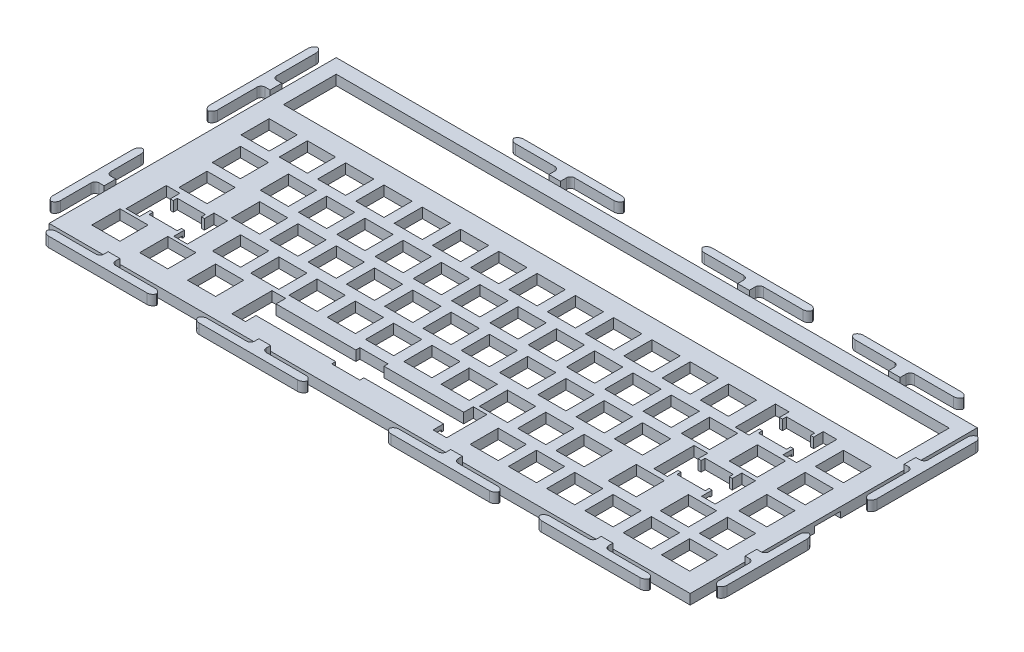
SolidWorks part; units mm, degrees
ref_plane "Front Plane" through (0, 0, 0) normal (0, 0, 1) x (1, 0, 0)
ref_plane "Top Plane" through (0, 0, 0) normal (0, 1, 0) x (1, 0, 0)
ref_plane "Right Plane" through (0, 0, 0) normal (1, 0, 0) x (0, 0, -1)
sketch "Sketch1" plane through (0, 0, 0) normal (0, 1, 0) x (1, 0, 0)
  line L2 (-75.7545, 37.9956) -> (-61.7545, 37.9956)
  line L3 (-94.8265, 37.9956) -> (-80.8265, 37.9956)
  line L4 (-94.8265, 37.9956) -> (-94.8265, 51.9956)
  line L5 (-94.8265, 51.9956) -> (-80.8265, 51.9956)
  line L6 (-80.8265, 37.9956) -> (-80.8265, 51.9956)
  line L7 (-75.7545, 37.9956) -> (-75.7545, 51.9956)
  line L8 (-75.7545, 51.9956) -> (-61.7545, 51.9956)
  line L9 (-61.7545, 37.9956) -> (-61.7545, 51.9956)
  line L10 (133.7495, 37.9956) -> (147.7495, 37.9956)
  line L11 (-37.6545, 37.9956) -> (-23.6545, 37.9956)
  line L12 (-56.7045, 37.9956) -> (-42.7045, 37.9956)
  line L13 (-56.7045, 37.9956) -> (-56.7045, 51.9956)
  line L14 (-56.7045, 51.9956) -> (-42.7045, 51.9956)
  line L15 (-42.7045, 37.9956) -> (-42.7045, 51.9956)
  line L16 (-37.6545, 37.9956) -> (-37.6545, 51.9956)
  line L17 (-37.6545, 51.9956) -> (-23.6545, 51.9956)
  line L18 (-23.6545, 37.9956) -> (-23.6545, 51.9956)
  line L19 (133.7495, 37.9956) -> (133.7495, 51.9956)
  line L20 (133.7495, 51.9956) -> (147.7495, 51.9956)
  line L21 (0.4455, 37.9956) -> (14.4455, 37.9956)
  line L22 (-18.6045, 37.9956) -> (-4.6045, 37.9956)
  line L23 (-18.6045, 37.9956) -> (-18.6045, 51.9956)
  line L24 (-18.6045, 51.9956) -> (-4.6045, 51.9956)
  line L25 (-4.6045, 37.9956) -> (-4.6045, 51.9956)
  line L26 (0.4455, 37.9956) -> (0.4455, 51.9956)
  line L27 (0.4455, 51.9956) -> (14.4455, 51.9956)
  line L28 (14.4455, 37.9956) -> (14.4455, 51.9956)
  line L29 (147.7495, 37.9956) -> (147.7495, 51.9956)
  line L30 (38.5455, 37.9956) -> (52.5455, 37.9956)
  line L31 (19.4955, 37.9956) -> (33.4955, 37.9956)
  line L32 (19.4955, 37.9956) -> (19.4955, 51.9956)
  line L33 (19.4955, 51.9956) -> (33.4955, 51.9956)
  line L34 (33.4955, 37.9956) -> (33.4955, 51.9956)
  line L35 (38.5455, 37.9956) -> (38.5455, 51.9956)
  line L36 (38.5455, 51.9956) -> (52.5455, 51.9956)
  line L37 (52.5455, 37.9956) -> (52.5455, 51.9956)
  line L38 (147.7495, 44.9956) -> (154.1495, 44.9956) construction
  line L39 (167.1835, 18.9456) -> (181.1835, 18.9456)
  line L40 (167.1835, 18.9456) -> (167.1835, 32.9456)
  line L41 (76.6455, 37.9956) -> (90.6455, 37.9956)
  line L42 (57.5955, 37.9956) -> (71.5955, 37.9956)
  line L43 (57.5955, 37.9956) -> (57.5955, 51.9956)
  line L44 (57.5955, 51.9956) -> (71.5955, 51.9956)
  line L45 (71.5955, 37.9956) -> (71.5955, 51.9956)
  line L46 (76.6455, 37.9956) -> (76.6455, 51.9956)
  line L47 (76.6455, 51.9956) -> (90.6455, 51.9956)
  line L48 (90.6455, 37.9956) -> (90.6455, 51.9956)
  line L49 (167.1835, 32.9456) -> (181.1835, 32.9456)
  line L50 (114.7225, 37.9956) -> (128.7225, 37.9956)
  line L51 (95.6955, 37.9956) -> (109.6955, 37.9956)
  line L52 (95.6955, 37.9956) -> (95.6955, 51.9956)
  line L53 (95.6955, 51.9956) -> (109.6955, 51.9956)
  line L54 (109.6955, 37.9956) -> (109.6955, 51.9956)
  line L55 (114.7225, 37.9956) -> (114.7225, 51.9956)
  line L56 (114.7225, 51.9956) -> (128.7225, 51.9956)
  line L57 (128.7225, 37.9956) -> (128.7225, 51.9956)
  line L58 (181.1835, 18.9456) -> (181.1835, 32.9456)
  line L59 (157.3735, 25.9456) -> (167.1835, 25.9456) construction
  line L73 (162.3995, 52.2456) -> (176.3995, 52.2456)
  line L75 (176.3995, 38.2456) -> (162.3995, 38.2456)
  line L77 (176.3995, 52.2456) -> (176.3995, 50.2456)
  line L78 (176.3995, 50.2456) -> (177.8995, 50.2456)
  line L79 (177.8995, 50.2456) -> (177.8995, 54.9956)
  line L80 (177.8995, 54.9956) -> (184.6495, 54.9956)
  line L81 (184.6495, 54.9956) -> (184.6495, 34.9956)
  line L82 (184.6495, 34.9956) -> (177.8995, 34.9956)
  line L83 (177.8995, 34.9956) -> (177.8995, 40.2456)
  line L84 (177.8995, 40.2456) -> (176.3995, 40.2456)
  line L85 (176.3995, 40.2456) -> (176.3995, 38.2456)
  line L86 (162.3995, 52.2456) -> (162.3995, 50.2456)
  line L87 (160.8995, 54.9956) -> (160.8995, 50.2456)
  line L88 (160.8995, 50.2456) -> (162.3995, 50.2456)
  line L89 (160.8995, 54.9956) -> (154.1495, 54.9956)
  line L90 (154.1495, 54.9956) -> (154.1495, 34.9956)
  line L91 (154.1495, 34.9956) -> (160.8995, 34.9956)
  line L92 (160.8995, 34.9956) -> (160.8995, 40.2456)
  line L93 (160.8995, 40.2456) -> (162.3995, 40.2456)
  line L94 (162.3995, 40.2456) -> (162.3995, 38.2456)
  line L116 (-47.1265, 18.9456) -> (-33.1265, 18.9456)
  line L117 (-66.1765, 18.9456) -> (-52.1765, 18.9456)
  line L118 (-66.1765, 18.9456) -> (-66.1765, 32.9456)
  line L119 (-66.1765, 32.9456) -> (-52.1765, 32.9456)
  line L120 (-52.1765, 18.9456) -> (-52.1765, 32.9456)
  line L121 (-47.1265, 18.9456) -> (-47.1265, 32.9456)
  line L122 (-47.1265, 32.9456) -> (-33.1265, 32.9456)
  line L123 (-33.1265, 18.9456) -> (-33.1265, 32.9456)
  line L125 (-9.0515, 18.9456) -> (4.9485, 18.9456)
  line L126 (-28.0765, 18.9456) -> (-14.0765, 18.9456)
  line L127 (-28.0765, 18.9456) -> (-28.0765, 32.9456)
  line L128 (-28.0765, 32.9456) -> (-14.0765, 32.9456)
  line L129 (-14.0765, 18.9456) -> (-14.0765, 32.9456)
  line L130 (-9.0515, 18.9456) -> (-9.0515, 32.9456)
  line L131 (-9.0515, 32.9456) -> (4.9485, 32.9456)
  line L132 (4.9485, 18.9456) -> (4.9485, 32.9456)
  line L135 (29.0735, 18.9456) -> (43.0735, 18.9456)
  line L136 (9.9485, 18.9456) -> (23.9485, 18.9456)
  line L137 (9.9485, 18.9456) -> (9.9485, 32.9456)
  line L138 (9.9485, 32.9456) -> (23.9485, 32.9456)
  line L139 (23.9485, 18.9456) -> (23.9485, 32.9456)
  line L140 (29.0735, 18.9456) -> (29.0735, 32.9456)
  line L141 (29.0735, 32.9456) -> (43.0735, 32.9456)
  line L142 (43.0735, 18.9456) -> (43.0735, 32.9456)
  line L144 (67.1485, 18.9456) -> (81.1485, 18.9456)
  line L145 (48.1235, 18.9456) -> (62.1235, 18.9456)
  line L146 (48.1235, 18.9456) -> (48.1235, 32.9456)
  line L147 (48.1235, 32.9456) -> (62.1235, 32.9456)
  line L148 (62.1235, 18.9456) -> (62.1235, 32.9456)
  line L149 (67.1485, 18.9456) -> (67.1485, 32.9456)
  line L150 (67.1485, 32.9456) -> (81.1485, 32.9456)
  line L151 (81.1485, 18.9456) -> (81.1485, 32.9456)
  line L152 (159.9865, 14.1456) -> (173.9865, 14.1456)
  line L153 (-42.3635, -0.1044) -> (-28.3635, -0.1044)
  line L154 (-61.4135, -0.1044) -> (-47.4135, -0.1044)
  line L155 (105.2735, 18.9456) -> (119.2735, 18.9456)
  line L156 (86.2235, 18.9456) -> (100.2235, 18.9456)
  line L157 (86.2235, 18.9456) -> (86.2235, 32.9456)
  line L158 (86.2235, 32.9456) -> (100.2235, 32.9456)
  line L159 (100.2235, 18.9456) -> (100.2235, 32.9456)
  line L160 (105.2735, 18.9456) -> (105.2735, 32.9456)
  line L161 (105.2735, 32.9456) -> (119.2735, 32.9456)
  line L162 (119.2735, 18.9456) -> (119.2735, 32.9456)
  line L163 (-61.4135, -0.1044) -> (-61.4135, 13.8956)
  line L172 (-94.8265, 37.9956) -> (-94.8265, 32.9456) construction
  line L173 (-61.4135, 13.8956) -> (-47.4135, 13.8956)
  line L174 (-47.4135, -0.1044) -> (-47.4135, 13.8956)
  line L175 (-90.0635, 18.9456) -> (-76.0635, 18.9456)
  line L176 (-90.0635, 18.9456) -> (-90.0635, 32.9456)
  line L177 (-90.0635, 32.9456) -> (-76.0635, 32.9456)
  line L178 (-76.0635, 18.9456) -> (-76.0635, 32.9456)
  line L179 (-94.8265, 32.9456) -> (-90.0635, 32.9456) construction
  line L180 (124.3235, 18.9456) -> (138.3235, 18.9456)
  line L185 (124.3235, 18.9456) -> (124.3235, 32.9456)
  line L186 (124.3235, 32.9456) -> (138.3235, 32.9456)
  line L187 (138.3235, 18.9456) -> (138.3235, 32.9456)
  line L188 (-42.3635, -0.1044) -> (-42.3635, 13.8956)
  line L189 (143.3735, 18.9456) -> (157.3735, 18.9456)
  line L190 (143.3735, 18.9456) -> (143.3735, 32.9456)
  line L191 (143.3735, 32.9456) -> (157.3735, 32.9456)
  line L192 (157.3735, 18.9456) -> (157.3735, 32.9456)
  line L193 (-42.3635, 13.8956) -> (-28.3635, 13.8956)
  line L194 (-28.3635, -0.1044) -> (-28.3635, 13.8956)
  line L195 (-4.2635, -0.1044) -> (9.7365, -0.1044)
  line L196 (-23.3135, -0.1044) -> (-9.3135, -0.1044)
  line L197 (-23.3135, -0.1044) -> (-23.3135, 13.8956)
  line L198 (-23.3135, 13.8956) -> (-9.3135, 13.8956)
  line L199 (-9.3135, -0.1044) -> (-9.3135, 13.8956)
  line L200 (-4.2635, -0.1044) -> (-4.2635, 13.8956)
  line L201 (-4.2635, 13.8956) -> (9.7365, 13.8956)
  line L202 (9.7365, -0.1044) -> (9.7365, 13.8956)
  line L203 (33.8365, -0.1044) -> (47.8365, -0.1044)
  line L204 (14.7865, -0.1044) -> (28.7865, -0.1044)
  line L205 (14.7865, -0.1044) -> (14.7865, 13.8956)
  line L206 (14.7865, 13.8956) -> (28.7865, 13.8956)
  line L207 (28.7865, -0.1044) -> (28.7865, 13.8956)
  line L208 (33.8365, -0.1044) -> (33.8365, 13.8956)
  line L209 (33.8365, 13.8956) -> (47.8365, 13.8956)
  line L210 (47.8365, -0.1044) -> (47.8365, 13.8956)
  line L211 (71.9365, -0.1044) -> (85.9365, -0.1044)
  line L212 (52.8865, -0.1044) -> (66.8865, -0.1044)
  line L213 (52.8865, -0.1044) -> (52.8865, 13.8956)
  line L214 (52.8865, 13.8956) -> (66.8865, 13.8956)
  line L215 (66.8865, -0.1044) -> (66.8865, 13.8956)
  line L216 (71.9365, -0.1044) -> (71.9365, 13.8956)
  line L217 (71.9365, 13.8956) -> (85.9365, 13.8956)
  line L218 (85.9365, -0.1044) -> (85.9365, 13.8956)
  line L219 (110.0365, -0.1044) -> (124.0365, -0.1044)
  line L220 (90.9865, -0.1044) -> (104.9865, -0.1044)
  line L221 (90.9865, -0.1044) -> (90.9865, 13.8956)
  line L222 (90.9865, 13.8956) -> (104.9865, 13.8956)
  line L223 (104.9865, -0.1044) -> (104.9865, 13.8956)
  line L224 (110.0365, -0.1044) -> (110.0365, 13.8956)
  line L225 (110.0365, 13.8956) -> (124.0365, 13.8956)
  line L226 (124.0365, -0.1044) -> (124.0365, 13.8956)
  line L227 (-87.6075, -0.1044) -> (-73.6075, -0.1044)
  line L228 (-87.6075, -0.1044) -> (-87.6075, 13.8956)
  line L229 (-87.6075, 13.8956) -> (-73.6075, 13.8956)
  line L230 (-73.6075, -0.1044) -> (-73.6075, 13.8956)
  line L231 (-90.0635, 18.9456) -> (-90.0635, 13.8956) construction
  line L232 (129.0865, -0.1044) -> (143.0865, -0.1044)
  line L233 (129.0865, -0.1044) -> (129.0865, 13.8956)
  line L234 (129.0865, 13.8956) -> (143.0865, 13.8956)
  line L235 (143.0865, -0.1044) -> (143.0865, 13.8956)
  line L240 (-90.0635, 13.8956) -> (-87.6075, 13.8956) construction
  line L241 (173.9865, 0.1456) -> (159.9865, 0.1456)
  line L242 (173.9865, 14.1456) -> (173.9865, 12.1456)
  line L243 (173.9865, 12.1456) -> (175.4865, 12.1456)
  line L244 (175.4865, 12.1456) -> (175.4865, 16.8956)
  line L245 (175.4865, 16.8956) -> (182.2365, 16.8956)
  line L246 (182.2365, 16.8956) -> (182.2365, -3.1044)
  line L247 (182.2365, -3.1044) -> (175.4865, -3.1044)
  line L248 (175.4865, -3.1044) -> (175.4865, 2.1456)
  line L249 (175.4865, 2.1456) -> (173.9865, 2.1456)
  line L250 (173.9865, 2.1456) -> (173.9865, 0.1456)
  line L251 (159.9865, 14.1456) -> (159.9865, 12.1456)
  line L252 (158.4865, 16.8956) -> (158.4865, 12.1456)
  line L253 (158.4865, 12.1456) -> (159.9865, 12.1456)
  line L254 (158.4865, 16.8956) -> (151.7365, 16.8956)
  line L255 (151.7365, 16.8956) -> (151.7365, -3.1044)
  line L256 (151.7365, -3.1044) -> (158.4865, -3.1044)
  line L257 (158.4865, -3.1044) -> (158.4865, 2.1456)
  line L258 (158.4865, 2.1456) -> (159.9865, 2.1456)
  line L259 (159.9865, 2.1456) -> (159.9865, 0.1456)
  line L260 (143.0865, 12.1456) -> (151.7365, 12.1456) construction
  line L262 (-32.8385, -19.1544) -> (-18.8385, -19.1544)
  line L263 (-51.8885, -19.1544) -> (-37.8885, -19.1544)
  line L264 (-51.8885, -19.1544) -> (-51.8885, -5.1544)
  line L265 (-51.8885, -5.1544) -> (-37.8885, -5.1544)
  line L266 (-37.8885, -19.1544) -> (-37.8885, -5.1544)
  line L267 (-32.8385, -19.1544) -> (-32.8385, -5.1544)
  line L268 (-32.8385, -5.1544) -> (-18.8385, -5.1544)
  line L269 (-18.8385, -19.1544) -> (-18.8385, -5.1544)
  line L270 (5.2615, -19.1544) -> (19.2615, -19.1544)
  line L271 (-13.7885, -19.1544) -> (0.2115, -19.1544)
  line L272 (-13.7885, -19.1544) -> (-13.7885, -5.1544)
  line L273 (-13.7885, -5.1544) -> (0.2115, -5.1544)
  line L274 (0.2115, -19.1544) -> (0.2115, -5.1544)
  line L275 (5.2615, -19.1544) -> (5.2615, -5.1544)
  line L276 (5.2615, -5.1544) -> (19.2615, -5.1544)
  line L277 (19.2615, -19.1544) -> (19.2615, -5.1544)
  line L278 (43.3615, -19.1544) -> (57.3615, -19.1544)
  line L279 (24.3115, -19.1544) -> (38.3115, -19.1544)
  line L280 (24.3115, -19.1544) -> (24.3115, -5.1544)
  line L281 (24.3115, -5.1544) -> (38.3115, -5.1544)
  line L282 (38.3115, -19.1544) -> (38.3115, -5.1544)
  line L283 (43.3615, -19.1544) -> (43.3615, -5.1544)
  line L284 (43.3615, -5.1544) -> (57.3615, -5.1544)
  line L285 (57.3615, -19.1544) -> (57.3615, -5.1544)
  line L286 (81.4615, -19.6544) -> (95.4615, -19.6544)
  line L287 (62.4115, -19.6544) -> (76.4115, -19.6544)
  line L288 (62.4115, -19.6544) -> (62.4115, -5.6544)
  line L289 (62.4115, -5.6544) -> (76.4115, -5.6544)
  line L290 (76.4115, -19.6544) -> (76.4115, -5.6544)
  line L291 (81.4615, -19.6544) -> (81.4615, -5.6544)
  line L292 (81.4615, -5.6544) -> (95.4615, -5.6544)
  line L293 (95.4615, -19.6544) -> (95.4615, -5.6544)
  line L294 (119.5615, -19.6544) -> (133.5615, -19.6544)
  line L295 (100.5115, -19.6544) -> (114.5115, -19.6544)
  line L296 (100.5115, -19.6544) -> (100.5115, -5.6544)
  line L297 (100.5115, -5.6544) -> (114.5115, -5.6544)
  line L298 (114.5115, -19.6544) -> (114.5115, -5.6544)
  line L299 (119.5615, -19.6544) -> (119.5615, -5.6544)
  line L300 (119.5615, -5.6544) -> (133.5615, -5.6544)
  line L301 (133.5615, -19.6544) -> (133.5615, -5.6544)
  line L306 (-83.3445, -5.1544) -> (-69.3445, -5.1544)
  line L307 (145.5235, -19.6544) -> (159.5235, -19.6544)
  line L308 (145.5235, -19.6544) -> (145.5235, -5.6544)
  line L309 (145.5235, -5.6544) -> (159.5235, -5.6544)
  line L310 (159.5235, -19.6544) -> (159.5235, -5.6544)
  line L311 (-69.3445, -19.1544) -> (-83.3445, -19.1544)
  line L331 (171.4855, -19.6544) -> (185.4855, -19.6544)
  line L332 (171.4855, -19.6544) -> (171.4855, -5.6544)
  line L333 (171.4855, -5.6544) -> (185.4855, -5.6544)
  line L334 (185.4855, -19.6544) -> (185.4855, -5.6544)
  line L335 (159.5235, -12.6544) -> (171.4855, -12.6544) construction
  line L336 (-61.4135, -0.1044) -> (-61.4135, -5.1544) construction
  line L337 (-61.4135, -5.1544) -> (-51.8885, -5.1544) construction
  line L338 (-104.4215, 94.9896) -> (-117.5239, 94.9896) construction
  line L339 (-97.2765, 61.6456) -> (207.7235, 61.6456)
  line L340 (190.9955, 18.9456) -> (204.9955, 18.9456)
  line L341 (190.9955, 18.9456) -> (190.9955, 32.9456)
  line L342 (190.9955, 32.9456) -> (204.9955, 32.9456)
  line L343 (204.9955, 18.9456) -> (204.9955, 32.9456)
  line L344 (181.1835, 25.9456) -> (190.9955, 25.9456) construction
  line L345 (190.9745, 37.9956) -> (204.9745, 37.9956)
  line L346 (190.9745, 37.9956) -> (190.9745, 51.9956)
  line L347 (190.9745, 51.9956) -> (204.9745, 51.9956)
  line L348 (204.9745, 37.9956) -> (204.9745, 51.9956)
  line L349 (184.6495, 44.9956) -> (190.9745, 44.9956) construction
  line L350 (190.9425, -0.1044) -> (204.9425, -0.1044)
  line L351 (190.9425, -0.1044) -> (190.9425, 13.8956)
  line L352 (190.9425, 13.8956) -> (204.9425, 13.8956)
  line L353 (204.9425, -0.1044) -> (204.9425, 13.8956)
  line L354 (182.2365, 6.8956) -> (190.9425, 6.8956) construction
  line L355 (190.9855, -19.6544) -> (204.9855, -19.6544)
  line L356 (190.9855, -19.6544) -> (190.9855, -5.6544)
  line L357 (190.9855, -5.6544) -> (204.9855, -5.6544)
  line L358 (204.9855, -19.6544) -> (204.9855, -5.6544)
  line L359 (185.4855, -12.6544) -> (190.9855, -12.6544) construction
  line L360 (-69.3445, -5.1544) -> (-69.3445, -7.1544)
  line L361 (-69.3445, -7.1544) -> (-67.8445, -7.1544)
  line L362 (-67.8445, -7.1544) -> (-67.8445, -2.4044)
  line L363 (-67.8445, -2.4044) -> (-61.0945, -2.4044)
  line L364 (-61.0945, -2.4044) -> (-61.0945, -22.4044)
  line L365 (-61.0945, -22.4044) -> (-67.8445, -22.4044)
  line L366 (-67.8445, -22.4044) -> (-67.8445, -17.1544)
  line L367 (-67.8445, -17.1544) -> (-69.3445, -17.1544)
  line L368 (-69.3445, -17.1544) -> (-69.3445, -19.1544)
  line L369 (-83.3445, -5.1544) -> (-83.3445, -7.1544)
  line L370 (-84.8445, -2.4044) -> (-84.8445, -7.1544)
  line L371 (-84.8445, -7.1544) -> (-83.3445, -7.1544)
  line L372 (-84.8445, -2.4044) -> (-91.5945, -2.4044)
  line L373 (-91.5945, -2.4044) -> (-91.5945, -22.4044)
  line L374 (-91.5945, -22.4044) -> (-84.8445, -22.4044)
  line L375 (-84.8445, -22.4044) -> (-84.8445, -17.1544)
  line L376 (-84.8445, -17.1544) -> (-83.3445, -17.1544)
  line L377 (-83.3445, -17.1544) -> (-83.3445, -19.1544)
  line L378 (-93.0945, -37.9544) -> (-79.0945, -37.9544)
  line L379 (-93.0945, -37.9544) -> (-93.0945, -23.9544)
  line L380 (-93.0945, -23.9544) -> (-79.0945, -23.9544)
  line L381 (-79.0945, -37.9544) -> (-79.0945, -23.9544)
  line L382 (-69.2945, -37.9544) -> (-55.2945, -37.9544)
  line L383 (-69.2945, -37.9544) -> (-69.2945, -23.9544)
  line L384 (-69.2945, -23.9544) -> (-55.2945, -23.9544)
  line L385 (-55.2945, -37.9544) -> (-55.2945, -23.9544)
  line L390 (-45.4945, -37.9544) -> (-31.4945, -37.9544)
  line L391 (-45.4945, -37.9544) -> (-45.4945, -23.9544)
  line L392 (-45.4945, -23.9544) -> (-31.4945, -23.9544)
  line L393 (-31.4945, -37.9544) -> (-31.4945, -23.9544)
  line L394 (-55.2945, -23.9544) -> (-45.4945, -23.9544) construction
  line L395 (26.4395, -24.1144) -> (40.4395, -24.1144)
  line L396 (40.4395, -38.1144) -> (26.4395, -38.1144)
  line L397 (40.4395, -24.1144) -> (40.4395, -26.1144)
  line L398 (40.4395, -26.1144) -> (80.1235, -26.1144)
  line L399 (80.1235, -26.1144) -> (80.1235, -21.3644)
  line L400 (80.1235, -21.3644) -> (86.8735, -21.3644)
  line L401 (86.8735, -21.3644) -> (86.8735, -41.3644)
  line L402 (86.8735, -41.3644) -> (80.1235, -41.3644)
  line L403 (80.1235, -41.3644) -> (80.1235, -36.1144)
  line L404 (80.1235, -36.1144) -> (40.4395, -36.1144)
  line L405 (40.4395, -36.1144) -> (40.4395, -38.1144)
  line L406 (26.4395, -24.1144) -> (26.4395, -26.1144)
  line L407 (-13.2445, -21.3644) -> (-13.2445, -26.1144)
  line L408 (-13.2445, -26.1144) -> (26.4395, -26.1144)
  line L409 (-13.2445, -21.3644) -> (-19.9945, -21.3644)
  line L410 (-19.9945, -21.3644) -> (-19.9945, -41.3644)
  line L411 (-19.9945, -41.3644) -> (-13.2445, -41.3644)
  line L412 (-13.2445, -41.3644) -> (-13.2445, -36.1144)
  line L413 (-13.2445, -36.1144) -> (26.4395, -36.1144)
  line L414 (26.4395, -36.1144) -> (26.4395, -38.1144)
  line L415 (95.5435, -38.3644) -> (109.5435, -38.3644)
  line L416 (95.5435, -38.3644) -> (95.5435, -24.3644)
  line L417 (95.5435, -24.3644) -> (109.5435, -24.3644)
  line L418 (109.5435, -38.3644) -> (109.5435, -24.3644)
  line L419 (86.8735, -31.3644) -> (95.5435, -31.3644) construction
  line L420 (114.5935, -38.3644) -> (128.5935, -38.3644)
  line L421 (114.5935, -38.3644) -> (114.5935, -24.3644)
  line L422 (114.5935, -24.3644) -> (128.5935, -24.3644)
  line L423 (128.5935, -38.3644) -> (128.5935, -24.3644)
  line L424 (114.5935, -31.3644) -> (109.5435, -31.3644) construction
  line L425 (133.6435, -38.3644) -> (147.6435, -38.3644)
  line L426 (133.6435, -38.3644) -> (133.6435, -24.3644)
  line L427 (133.6435, -24.3644) -> (147.6435, -24.3644)
  line L428 (147.6435, -38.3644) -> (147.6435, -24.3644)
  line L429 (152.6935, -38.3644) -> (166.6935, -38.3644)
  line L430 (152.6935, -38.3644) -> (152.6935, -24.3644)
  line L431 (152.6935, -24.3644) -> (166.6935, -24.3644)
  line L432 (166.6935, -38.3644) -> (166.6935, -24.3644)
  line L433 (171.7435, -38.3644) -> (185.7435, -38.3644)
  line L434 (171.7435, -38.3644) -> (171.7435, -24.3644)
  line L435 (171.7435, -24.3644) -> (185.7435, -24.3644)
  line L436 (185.7435, -38.3644) -> (185.7435, -24.3644)
  line L437 (190.7935, -38.3644) -> (204.7935, -38.3644)
  line L438 (190.7935, -38.3644) -> (190.7935, -24.3644)
  line L439 (190.7935, -24.3644) -> (204.7935, -24.3644)
  line L440 (204.7935, -38.3644) -> (204.7935, -24.3644)
  line L441 (-97.2765, 61.6456) -> (-97.2765, 87.8456)
  line L442 (-97.2765, 87.8456) -> (207.7235, 87.8456)
  line L443 (207.7235, 61.6456) -> (207.7235, 87.8456)
  line L444 (-104.4215, 94.9896) -> (214.5785, 94.9896)
  line L445 (-104.4215, 94.9896) -> (-104.4215, -47.8854)
  line L446 (-104.4215, -47.8854) -> (214.5785, -47.8854)
  line L447 (214.5785, 94.9896) -> (214.5785, -47.8854)
  line L448 (-117.5239, 94.9896) -> (-117.5239, 25.8096) construction
  line L449 (-104.4215, -47.8854) -> (-117.5239, -47.8854) construction
  line L450 (-117.5239, -47.8854) -> (-117.5239, 14.6046) construction
  line L451 (-150.5498, 25.8096) -> (-98.6233, 25.8096) construction
  line L452 (-150.5498, 14.6046) -> (-97.2765, 14.6046) construction
  line L453 (-104.4215, 94.9896) -> (-104.4215, 60.3996) construction
  point P115 (128.7225, 44.9956)
  point P116 (154.1495, 44.9956)
  dimension "D1" = 14
  dimension "D2" = 20
  dimension "D3" = 4.75
  dimension "D4" = 6.75
  dimension "D5" = 1.5
  dimension "D6" = 2
  dimension "D13" = 14
  dimension "D14" = 14
  dimension "D15" = 5.072
  dimension "D16" = 14
  dimension "D17" = 5.05
  dimension "D18" = 5.05
  dimension "D19" = 14
  dimension "D20" = 4.763
  dimension "D21" = 5.05
  dimension "D22" = 9.887
  dimension "D23" = 26.2
  dimension "D24" = 14
  dimension "D25" = 14
  dimension "D26" = 5.05
  dimension "D27" = 5.05
  dimension "D28" = 5.05
  dimension "D29" = 5.05
  dimension "D30" = 5.05
  dimension "D31" = 5.05
  dimension "D32" = 5.05
  dimension "D33" = 5.05
  dimension "D34" = 5.05
  dimension "D35" = 5.027
  dimension "D36" = 5.05
  dimension "D37" = 5.05
  dimension "D38" = 5.025
  dimension "D39" = 5
  dimension "D40" = 5.125
  dimension "D41" = 5.05
  dimension "D42" = 5.025
  dimension "D43" = 5.075
  dimension "D44" = 5.05
  dimension "D45" = 5.05
  dimension "D46" = 5.027
  dimension "D47" = 14.65
  dimension "D48" = 14
  dimension "D49" = 9.81
  dimension "D50" = 12.194
  dimension "D51" = 5.05
  dimension "D52" = 5.05
  dimension "D53" = 5.05
  dimension "D54" = 5.05
  dimension "D55" = 5.05
  dimension "D56" = 5.05
  dimension "D57" = 5.05
  dimension "D58" = 5.05
  dimension "D59" = 5.05
  dimension "D60" = 5.05
  dimension "D61" = 14
  dimension "D62" = 20
  dimension "D63" = 5.05
  dimension "D64" = 2.456
  dimension "D65" = 4.75
  dimension "D66" = 6.75
  dimension "D67" = 1.5
  dimension "D68" = 2
  dimension "D69" = 16.9
  dimension "D70" = 14
  dimension "D71" = 5.05
  dimension "D72" = 5.05
  dimension "D73" = 5.05
  dimension "D74" = 5.05
  dimension "D75" = 5.05
  dimension "D76" = 5.05
  dimension "D77" = 5.05
  dimension "D78" = 5.05
  dimension "D79" = 5.05
  dimension "D80" = 11.962
  dimension "D81" = 20
  dimension "D82" = 14
  dimension "D83" = 11.962
  dimension "D84" = 14
  dimension "D85" = 14
  dimension "D86" = 9.812
  dimension "D87" = 14
  dimension "D88" = 14.575
  dimension "D89" = 4.75
  dimension "D90" = 14
  dimension "D91" = 6.75
  dimension "D92" = 14
  dimension "D93" = 16.956
  dimension "D94" = 14
  dimension "D95" = 5.5
  dimension "D96" = 5.05
  dimension "D97" = 5.05
  dimension "D98" = 9.525
  dimension "D99" = 1.5
  dimension "D100" = 2
  dimension "D101" = 5.05
  dimension "D102" = 9.206
  dimension "D103" = 5.05
  dimension "D104" = 14
  dimension "D105" = 14
  dimension "D106" = 14
  dimension "D107" = 14
  dimension "D108" = 1.5
  dimension "D109" = 9.8
  dimension "D110" = 5.05
  dimension "D111" = 9.8
  dimension "D112" = 5.05
  dimension "D113" = 5.05
  dimension "D114" = 14
  dimension "D115" = 14
  dimension "D116" = 20
  dimension "D117" = 4.75
  dimension "D118" = 6.75
  dimension "D119" = 39.684
  dimension "D120" = 2
  dimension "D121" = 5.05
  dimension "D122" = 11.5
  dimension "D123" = 14
  dimension "D124" = 8.67
  dimension "D125" = 5.25
  dimension "D126" = 14
  dimension "D127" = 5.05
  dimension "D128" = 14
  dimension "D129" = 14
  dimension "D130" = 14
  dimension "D131" = 14
  dimension "D132" = 5.05
  dimension "D133" = 5.05
  dimension "D134" = 5.05
  dimension "D135" = 5.05
  dimension "D136" = 4.8
  dimension "D137" = 5.25
  dimension "D138" = 5.25
  dimension "D139" = 5.25
  dimension "D140" = 305
  dimension "D141" = 9.65
  dimension "D142" = 142.875
  dimension "D143" = 319
  dimension "D144" = 7.144
  dimension "D145" = 7.145
  dimension "D146" = 2.45
  dimension "D147" = 69.18
  dimension "D148" = 62.49
extrude "Boss-Extrude2" add sketch "Sketch1" along normal mid plane 5
sketch "Sketch2" plane through (0, 2.5, 0) normal (0, 1, 0) x (1, 0, 0)
  line L0 (-104.4215, 25.7896) -> (-104.4215, 14.6146) construction
  line L1 (-104.4215, -47.8854) -> (-104.4215, -20.4854) construction
  line L2 (-104.4215, 94.9896) -> (-104.4215, -47.8854) construction
  line L14 (-107.4215, 20.2021) -> (-104.4215, 20.2021) construction
  line L16 (-107.4215, 31.2421) -> (-107.4215, 9.1621) construction
  line L25 (214.5785, 64.3896) -> (214.5785, 58.5896)
  line L26 (55.1185, 125.3194) -> (55.1185, -78.0627) construction
  line L44 (214.5785, 58.5896) -> (218.6785, 58.5896)
  line L45 (218.6785, 58.5896) -> (218.6785, 33.9896)
  line L46 (218.6785, 33.9896) -> (222.6785, 33.9896)
  line L47 (222.6785, 33.9896) -> (222.6785, 88.9896)
  line L48 (55.0785, 94.9896) -> (55.0785, -47.8854) construction
  line L49 (214.5785, 94.9896) -> (-104.4215, 94.9896) construction
  line L50 (-104.4215, -47.8854) -> (214.5785, -47.8854) construction
  line L51 (55.1185, 23.6283) -> (270.1989, 23.6283) construction
  line L52 (55.1185, 23.6283) -> (-168.679, 23.6283) construction
  line L55 (45.7235, 94.9896) -> (56.8285, 94.9896) construction
  line L56 (51.276, 94.9896) -> (51.276, 98.9896) construction
  line L57 (40.236, 98.9896) -> (62.316, 98.9896) construction
  line L74 (222.6785, 88.9896) -> (218.6785, 88.9896)
  line L75 (214.5785, 94.9896) -> (176.1966, 94.9896) construction
  line L124 (55.0785, -47.8854) -> (95.4285, -47.8854) construction
  line L125 (-104.4215, 67.8896) -> (-104.4215, 62.0896)
  line L127 (45.7225, -47.8854) -> (56.8335, -47.8854) construction
  line L128 (51.278, -47.8854) -> (51.278, -52.8854) construction
  line L129 (40.276, -52.8854) -> (62.356, -52.8854) construction
  line L134 (-104.4215, 62.0896) -> (-108.9215, 62.0896)
  line L135 (-108.9215, 62.0896) -> (-108.9215, 37.4896)
  line L136 (-108.9215, 37.4896) -> (-112.9215, 37.4896)
  line L137 (-112.9215, 37.4896) -> (-112.9215, 92.4896)
  line L138 (-112.9215, 92.4896) -> (-108.9215, 92.4896)
  line L139 (-108.9215, 92.4896) -> (-108.9215, 67.8896)
  line L140 (-108.9215, 67.8896) -> (-104.4215, 67.8896)
  line L141 (-104.4215, 94.9896) -> (-104.4215, 67.8896) construction
  line L142 (-104.4215, -14.6854) -> (-104.4215, -20.4854)
  line L143 (-104.4215, -20.4854) -> (-108.9215, -20.4854)
  line L144 (-108.9215, -20.4854) -> (-108.9215, -40.5854)
  line L145 (-108.9215, -40.5854) -> (-112.9215, -40.5854)
  line L146 (-112.9215, -40.5854) -> (-112.9215, 5.4146)
  line L147 (-112.9215, 5.4146) -> (-108.9215, 5.4146)
  line L148 (-108.9215, 5.4146) -> (-108.9215, -14.6854)
  line L149 (-108.9215, -14.6854) -> (-104.4215, -14.6854)
  line L150 (1.3585, 94.9896) -> (7.1585, 94.9896)
  line L151 (7.1585, 94.9896) -> (7.1585, 99.9896)
  line L152 (7.1585, 99.9896) -> (31.7585, 99.9896)
  line L153 (31.7585, 99.9896) -> (31.7585, 103.9896)
  line L154 (31.7585, 103.9896) -> (-23.2415, 103.9896)
  line L155 (-23.2415, 103.9896) -> (-23.2415, 99.9896)
  line L156 (-23.2415, 99.9896) -> (1.3585, 99.9896)
  line L157 (1.3585, 99.9896) -> (1.3585, 94.9896)
  line L158 (55.0785, 94.9896) -> (7.1585, 94.9896) construction
  line L166 (-75.0215, -47.8854) -> (-69.2215, -47.8854)
  line L167 (-69.2215, -47.8854) -> (-69.2215, -51.9854)
  line L168 (-69.2215, -51.9854) -> (-44.6215, -51.9854)
  line L169 (-44.6215, -51.9854) -> (-44.6215, -55.9854)
  line L170 (-44.6215, -55.9854) -> (-99.6215, -55.9854)
  line L171 (-99.6215, -55.9854) -> (-99.6215, -51.9854)
  line L172 (-99.6215, -51.9854) -> (-75.0215, -51.9854)
  line L173 (-75.0215, -51.9854) -> (-75.0215, -47.8854)
  line L174 (-0.0215, -47.8854) -> (5.7785, -47.8854)
  line L175 (5.7785, -47.8854) -> (5.7785, -51.9854)
  line L176 (5.7785, -51.9854) -> (30.3785, -51.9854)
  line L177 (30.3785, -51.9854) -> (30.3785, -55.9854)
  line L178 (30.3785, -55.9854) -> (-24.6215, -55.9854)
  line L179 (-24.6215, -55.9854) -> (-24.6215, -51.9854)
  line L180 (-24.6215, -51.9854) -> (-0.0215, -51.9854)
  line L181 (-0.0215, -51.9854) -> (-0.0215, -47.8854)
  line L182 (-104.4215, -47.8854) -> (-75.0215, -47.8854) construction
  line L183 (95.4285, -47.8854) -> (101.2285, -47.8854)
  line L184 (101.2285, -47.8854) -> (101.2285, -51.9854)
  line L185 (101.2285, -51.9854) -> (125.8285, -51.9854)
  line L186 (125.8285, -51.9854) -> (125.8285, -55.9854)
  line L187 (125.8285, -55.9854) -> (70.8285, -55.9854)
  line L188 (70.8285, -55.9854) -> (70.8285, -51.9854)
  line L189 (70.8285, -51.9854) -> (95.4285, -51.9854)
  line L190 (95.4285, -51.9854) -> (95.4285, -47.8854)
  line L191 (170.3285, -47.8854) -> (176.1285, -47.8854)
  line L192 (176.1285, -47.8854) -> (176.1285, -51.9854)
  line L193 (176.1285, -51.9854) -> (200.7285, -51.9854)
  line L194 (200.7285, -51.9854) -> (200.7285, -55.9854)
  line L195 (200.7285, -55.9854) -> (145.7285, -55.9854)
  line L196 (145.7285, -55.9854) -> (145.7285, -51.9854)
  line L197 (145.7285, -51.9854) -> (170.3285, -51.9854)
  line L198 (170.3285, -51.9854) -> (170.3285, -47.8854)
  line L199 (55.0785, -47.8854) -> (5.7785, -47.8854) construction
  line L200 (95.3145, 94.9896) -> (101.1145, 94.9896)
  line L201 (101.1145, 94.9896) -> (101.1145, 99.9896)
  line L202 (101.1145, 99.9896) -> (125.7145, 99.9896)
  line L203 (125.7145, 99.9896) -> (125.7145, 103.9896)
  line L204 (125.7145, 103.9896) -> (70.7145, 103.9896)
  line L205 (70.7145, 103.9896) -> (70.7145, 99.9896)
  line L206 (70.7145, 99.9896) -> (95.3145, 99.9896)
  line L207 (95.3145, 99.9896) -> (95.3145, 94.9896)
  line L208 (170.3966, 94.9896) -> (176.1966, 94.9896)
  line L209 (176.1966, 94.9896) -> (176.1966, 99.9896)
  line L210 (176.1966, 99.9896) -> (200.7966, 99.9896)
  line L211 (200.7966, 99.9896) -> (200.7966, 103.9896)
  line L212 (200.7966, 103.9896) -> (145.7966, 103.9896)
  line L213 (145.7966, 103.9896) -> (145.7966, 99.9896)
  line L214 (145.7966, 99.9896) -> (170.3966, 99.9896)
  line L215 (170.3966, 99.9896) -> (170.3966, 94.9896)
  line L216 (214.5785, -47.8854) -> (176.1285, -47.8854) construction
  line L217 (218.6785, 88.9896) -> (218.6785, 64.3896)
  line L218 (218.6785, 64.3896) -> (214.5785, 64.3896)
  line L219 (214.5785, -14.7854) -> (214.5785, -20.5854)
  line L220 (214.5785, -20.5854) -> (218.6785, -20.5854)
  line L221 (218.6785, -20.5854) -> (218.6785, -40.6854)
  line L222 (218.6785, -40.6854) -> (222.6785, -40.6854)
  line L223 (222.6785, -40.6854) -> (222.6785, 5.3146)
  line L224 (222.6785, 5.3146) -> (218.6785, 5.3146)
  line L225 (218.6785, 5.3146) -> (218.6785, -14.7854)
  line L226 (218.6785, -14.7854) -> (214.5785, -14.7854)
  line L227 (214.5785, 94.9896) -> (214.5785, 64.3896) construction
  line L228 (214.5785, -47.8854) -> (214.5785, 94.9896) construction
  line L229 (214.5785, -47.8854) -> (214.5785, -20.5854) construction
  point P28 (-104.4215, 20.2021)
  point P84 (51.276, 98.9896)
  dimension "D4" = 5.8
  dimension "D5" = 4.5
  dimension "D6" = 55
  dimension "D7" = 22.08
  dimension "D8" = 4
  dimension "D9" = 5.8
  dimension "D10" = 4.5
  dimension "D11" = 4
  dimension "D12" = 46
  dimension "D13" = 27.1
  dimension "D14" = 5.8
  dimension "D15" = 4.1
  dimension "D16" = 4
  dimension "D17" = 27.4
  dimension "D18" = 47.92
  dimension "D19" = 4
  dimension "D20" = 22.08
  dimension "D21" = 40.196
  dimension "D22" = 55
  dimension "D23" = 5.8
  dimension "D24" = 4
  dimension "D25" = 46
  dimension "D26" = 30.6
  dimension "D27" = 27.3
  dimension "D29" = 4.1
  dimension "D31" = 38.45
  dimension "D32" = 5.8
  dimension "D33" = 5
  dimension "D34" = 22.08
  dimension "D35" = 5.8
  dimension "D36" = 5
  dimension "D37" = 4
  dimension "D38" = 55
  dimension "D39" = 40.35
  dimension "D40" = 5.8
  dimension "D41" = 4
  dimension "D42" = 55
  dimension "D43" = 4
  dimension "D44" = 55
  dimension "D45" = 4.1
  dimension "D46" = 4.1
  dimension "D47" = 29.4
  dimension "D48" = 5.8
  dimension "D49" = 4
  dimension "D50" = 55
  dimension "D51" = 4.1
  dimension "D52" = 5.8
  dimension "D53" = 4
  dimension "D54" = 55
  dimension "D55" = 4.1
  dimension "D56" = 49.3
  dimension "D57" = 5
  dimension "D58" = 55
  dimension "D59" = 5
  dimension "D60" = 55
extrude "Boss-Extrude3" add sketch "Sketch2" along normal mid plane 5
sketch "Sketch3" plane through (0, 2.5, 0) normal (0, 1, 0) x (1, 0, 0)
  line L0 (208.0785, 94.9896) -> (208.0785, 26.9896) construction
  line L1 (214.5785, 94.9896) -> (176.1966, 94.9896) construction
  line L2 (208.0785, 26.9896) -> (208.0785, 13.9896) construction
  line L3 (214.5785, -14.7854) -> (214.5785, 58.5896) construction
  line L4 (208.0785, 26.9896) -> (208.0785, 13.9896)
  line L5 (208.0785, 13.9896) -> (214.5785, 13.9896)
  line L6 (214.5785, 13.9896) -> (214.5785, 26.9896)
  line L7 (214.5785, 26.9896) -> (208.0785, 26.9896)
  line L8 (58.5785, 89.4896) -> (214.5785, 89.4896) construction
  line L9 (214.5785, 64.3896) -> (214.5785, 94.9896) construction
  line L10 (95.3145, 94.9896) -> (7.1585, 94.9896) construction
  line L11 (58.5785, 89.4896) -> (46.5792, 89.4896)
  line L12 (46.5792, 89.4896) -> (46.5792, 94.9896)
  line L13 (46.5792, 94.9896) -> (58.5785, 94.9896)
  line L14 (58.5785, 94.9896) -> (58.5785, 89.4896)
  line L15 (-97.4215, 94.9896) -> (-97.4215, 26.9896) construction
  line L16 (1.3585, 94.9896) -> (-104.4215, 94.9896) construction
  line L17 (-97.4215, 26.9896) -> (-97.4215, 13.9896) construction
  line L18 (-104.4215, 62.0896) -> (-104.4215, -14.6854) construction
  line L19 (-97.4215, 26.9896) -> (-104.4215, 26.9896)
  line L20 (-104.4215, 26.9896) -> (-104.4215, 13.9896)
  line L21 (-104.4215, 13.9896) -> (-97.4215, 13.9896)
  line L22 (-97.4215, 13.9896) -> (-97.4215, 26.9896)
  dimension "D1" = 68
  dimension "D2" = 13
  dimension "D3" = 6.5
  dimension "D4" = 156
  dimension "D5" = 5.5
  dimension "D6" = 180
  dimension "D7" = 7
extrude "Cut-Extrude1" cut sketch "Sketch3" against normal through all
sketch "Sketch4" plane through (175.4865, 0, 0) normal (1, 0, 0) x (0, 0, -1)
  line L12 (2.1456, -2.5) -> (-3.1044, -2.5)
  line L15 (-3.1044, -2.5) -> (-3.1044, 0.5)
  line L16 (-3.1044, 2.5) -> (-3.1044, -2.5) construction
  line L17 (-3.1044, 0.5) -> (1.1456, 0.5)
  line L18 (1.1456, 0.5) -> (1.1456, 0)
  line L19 (1.1456, 0) -> (2.1456, 0)
  line L20 (2.1456, 2.5) -> (2.1456, -2.5) construction
  line L21 (2.1456, 0) -> (2.1456, -2.5)
  dimension "D1" = 3
  dimension "D2" = 4.25
extrude "Cut-Extrude2" cut sketch "Sketch4" against normal blind 18
sketch "Sketch6" plane through (177.8995, 0, 0) normal (1, 0, 0) x (0, 0, -1)
  line L8 (34.9956, -2.5) -> (34.9956, 0.5)
  line L9 (34.9956, 2.5) -> (34.9956, -2.5) construction
  line L11 (34.9956, 0.5) -> (39.2456, 0.5)
  line L12 (39.2456, 0.5) -> (39.2456, -0.5)
  line L13 (39.2456, -0.5) -> (40.2456, -0.5)
  line L14 (40.2456, 2.5) -> (40.2456, -2.5) construction
  line L15 (40.2456, -0.5) -> (40.2456, -2.5)
  line L16 (40.2456, -2.5) -> (34.9956, -2.5)
  dimension "D1" = 4.25
  dimension "D2" = 3
  dimension "D3" = 2
extrude "Cut-Extrude3" cut sketch "Sketch6" against normal blind 18
sketch "Sketch7" plane through (-67.8445, 0, 0) normal (1, 0, 0) x (0, 0, -1)
  line L12 (-22.4044, -2.5) -> (-22.4044, 0.5)
  line L13 (-22.4044, 0.5) -> (-18.1544, 0.5)
  line L14 (-18.1544, 0.5) -> (-18.1544, -0.5)
  line L15 (-18.1544, -0.5) -> (-17.1544, -0.5)
  line L16 (-17.1544, -0.5) -> (-17.1544, -2.5)
  line L17 (-17.1544, -2.5) -> (-22.4044, -2.5)
  dimension "D4" = 4.25
  dimension "D5" = 3
  dimension "D6" = 2
extrude "Cut-Extrude4" cut sketch "Sketch7" against normal blind 18
sketch "Sketch8" plane through (80.1235, 0, 0) normal (1, 0, 0) x (0, 0, -1)
  line L6 (-41.3644, -2.5) -> (-41.3644, 0.5)
  line L7 (-41.3644, 0.5) -> (-37.1144, 0.5)
  line L8 (-37.1144, 0.5) -> (-37.1144, -0.5)
  line L9 (-37.1144, -0.5) -> (-36.1144, -0.5)
  line L10 (-36.1144, -0.5) -> (-36.1144, -2.5)
  line L11 (-36.1144, -2.5) -> (-41.3644, -2.5)
  dimension "D1" = 4.25
  dimension "D2" = 3
  dimension "D3" = 2
extrude "Cut-Extrude5" cut sketch "Sketch8" against normal blind 95
sketch "Sketch9" plane through (175.4865, 0, 0) normal (1, 0, 0) x (0, 0, -1)
fillet "Fillet1" radius 2 22 edges at (-108.9215, 2.5, 20.4854) (-108.9215, 2.5, 14.6854) (-75.0215, 2.5, 51.9854) (-69.2215, 2.5, 51.9854) (5.7785, 2.5, 51.9854) (-0.0215, 2.5, 51.9854) (95.4285, 2.5, 51.9854) (101.2285, 2.5, 51.9854) (176.1285, 2.5, 51.9854) (170.3285, 2.5, 51.9854) (218.6785, 2.5, 14.7854) (218.6785, 2.5, 20.5854) (218.6785, 2.5, -64.3896) (218.6785, 2.5, -58.5896) (176.1966, 2.5, -99.9896) (170.3966, 2.5, -99.9896) (101.1145, 2.5, -99.9896) (95.3145, 2.5, -99.9896) (1.3585, 2.5, -99.9896) (7.1585, 2.5, -99.9896) (-108.9215, 2.5, -67.8896) (-108.9215, 2.5, -62.0896)
fillet "Fillet2" radius 3 44 edges at (-112.9215, 2.5, -92.4896) (-108.9215, 2.5, -92.4896) (-108.9215, 2.5, -37.4896) (-112.9215, 2.5, -37.4896) (-108.9215, 2.5, -5.4146) (-112.9215, 2.5, -5.4146) (-108.9215, 2.5, 40.5854) (-112.9215, 2.5, 40.5854) (-44.6215, 2.5, 55.9854) (-44.6215, 2.5, 51.9854) (-99.6215, 2.5, 55.9854) (-99.6215, 2.5, 51.9854) (-24.6215, 2.5, 55.9854) (-24.6215, 2.5, 51.9854) (30.3785, 2.5, 55.9854) (30.3785, 2.5, 51.9854) (125.8285, 2.5, 55.9854) (125.8285, 2.5, 51.9854) (70.8285, 2.5, 55.9854) (70.8285, 2.5, 51.9854) (145.7285, 2.5, 55.9854) (145.7285, 2.5, 51.9854) (200.7285, 2.5, 55.9854) (200.7285, 2.5, 51.9854) (222.6785, 2.5, -5.3146) (218.6785, 2.5, -5.3146) (218.6785, 2.5, 40.6854) (222.6785, 2.5, 40.6854) (218.6785, 2.5, -33.9896) (222.6785, 2.5, -33.9896) (222.6785, 2.5, -88.9896) (218.6785, 2.5, -88.9896) (200.7966, 2.5, -103.9896) (200.7966, 2.5, -99.9896) (145.7966, 2.5, -99.9896) (145.7966, 2.5, -103.9896) (125.7145, 2.5, -99.9896) (125.7145, 2.5, -103.9896) (70.7145, 2.5, -99.9896) (70.7145, 2.5, -103.9896) (31.7585, 2.5, -99.9896) (31.7585, 2.5, -103.9896) (-23.2415, 2.5, -99.9896) (-23.2415, 2.5, -103.9896)
sketch "Sketch10" plane through (0, 2.5, 0) normal (0, 1, 0) x (1, 0, 0)
  line L0 (-104.4215, 26.9896) -> (-97.4215, 26.9896)
  line L1 (-97.4215, 26.9896) -> (-97.4215, 13.9896)
  line L2 (-97.4215, 13.9896) -> (-104.4215, 13.9896)
  line L3 (-104.4215, 13.9896) -> (-104.4215, 26.9896)
  line L4 (46.5792, 94.9896) -> (46.5792, 89.4896)
  line L5 (46.5792, 89.4896) -> (58.5785, 89.4896)
  line L6 (58.5785, 89.4896) -> (58.5785, 94.9896)
  line L7 (58.5785, 94.9896) -> (46.5792, 94.9896)
  line L8 (214.5785, 13.9896) -> (208.0785, 13.9896)
  line L9 (208.0785, 13.9896) -> (208.0785, 26.9896)
  line L10 (208.0785, 26.9896) -> (214.5785, 26.9896)
  line L11 (214.5785, 26.9896) -> (214.5785, 13.9896)
extrude "Boss-Extrude4" add sketch "Sketch10" against normal blind 2
